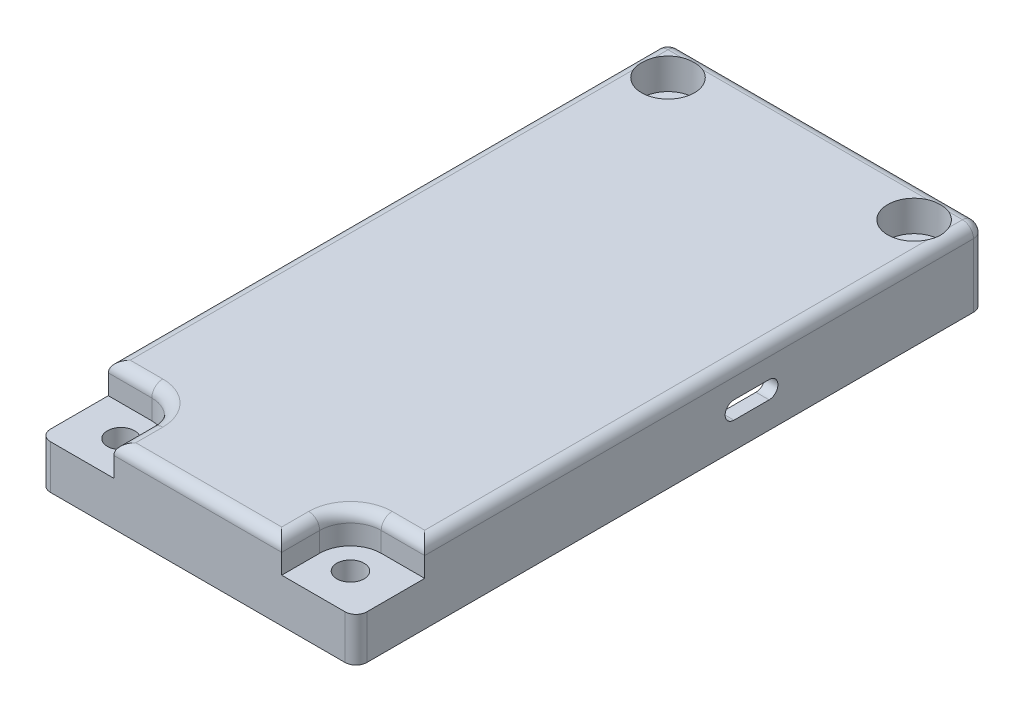
SolidWorks part; units mm, degrees
ref_plane "Front Plane" through (0, 0, 0) normal (0, 0, 1) x (1, 0, 0)
ref_plane "Top Plane" through (0, 0, 0) normal (0, 1, 0) x (1, 0, 0)
ref_plane "Right Plane" through (0, 0, 0) normal (1, 0, 0) x (0, 0, -1)
sketch "Sketch1" plane through (0, 0, 0) normal (0, 1, 0) x (1, 0, 0)
  line L1 (0, 0) -> (36, 0)
  line L2 (0, 0) -> (0, 71.5)
  line L3 (0, 71.5) -> (36, 71.5)
  line L4 (36, 0) -> (36, 71.5)
  dimension "D1" = 71.5
  dimension "D2" = 36
extrude "Boss-Extrude1" add sketch "Sketch1" along normal blind 8.5
sketch "Sketch2" plane through (0, 0, 0) normal (0, -1, 0) x (1, 0, 0)
  line L0 (0, -71.5) -> (0, 0) construction
  line L1 (1.5, -1.5) -> (34.5, -1.5)
  line L2 (1.5, -1.5) -> (1.5, -64.25)
  line L3 (1.5, -64.25) -> (34.5, -64.25)
  line L4 (34.5, -1.5) -> (34.5, -64.25)
  line L5 (0, 0) -> (36, 0) construction
  line L6 (36, 0) -> (36, -71.5) construction
  line L7 (36, -71.5) -> (0, -71.5) construction
  dimension "D1" = 1.5
  dimension "D2" = 1.5
  dimension "D3" = 1.5
  dimension "D4" = 7.25
extrude "Cut-Extrude1" cut sketch "Sketch2" against normal offset from surface (7 mm away) 1.5 up to face at (18, 8.5, -35.75)
sketch "Sketch4" plane through (0, 0, -71.5) normal (0, 0, -1) x (-1, 0, 0)
  line L0 (-36, 0) -> (0, 0) construction
  line L1 (-26, 0) -> (-10, 0)
  line L2 (-26, 0) -> (-26, 1.25)
  line L3 (-26, 1.25) -> (-10, 1.25)
  line L4 (-10, 0) -> (-10, 1.25)
  line L7 (-36, 8.5) -> (-36, 0) construction
  line L8 (0, 8.5) -> (0, 0) construction
  dimension "D1" = 10
  dimension "D2" = 10
  dimension "D3" = 1.25
extrude "Cut-Extrude2" cut sketch "Sketch4" against normal blind 6.5
fillet "Fillet1" radius 1.25 2 edges at (26, 1.25, -68.25) (10, 1.25, -68.25)
sketch "Sketch7" plane through (0, 7, 0) normal (0, -1, 0) x (1, 0, 0)
  line L0 (34.5, -1.5) -> (1.5, -1.5) construction
  line L1 (27.5, -1.5) -> (34.5, -1.5)
  line L2 (27.5, -1.5) -> (27.5, -8.5)
  line L3 (27.5, -8.5) -> (34.5, -8.5)
  line L4 (34.5, -1.5) -> (34.5, -8.5)
  line L5 (34.5, -1.5) -> (34.5, -64.25) construction
  line L6 (1.5, -1.5) -> (34.5, -1.5) construction
  line L7 (8.5, -1.5) -> (1.5, -1.5)
  line L8 (8.5, -1.5) -> (8.5, -8.5)
  line L9 (8.5, -8.5) -> (1.5, -8.5)
  line L10 (1.5, -1.5) -> (1.5, -8.5)
  line L11 (1.5, -64.25) -> (1.5, -1.5) construction
  dimension "D1" = 7
extrude "Boss-Extrude4" add sketch "Sketch7" along normal up to surface (7 mm away) up to face at (18, 0, -52)
sketch "Sketch8" plane through (0, 0, 0) normal (0, -1, 0) x (-1, 0, 0)
  line L0 (-36, 71.5) -> (-26, 71.5) construction
  line L1 (-36, 0) -> (-36, 71.5) construction
  line L2 (0, 71.5) -> (0, 0) construction
  line L3 (-8.5, 1.5) -> (-27.5, 1.5) construction
  circle A0 centre (-31.05, 4.32) radius 1.55
  circle A1 centre (-32, 67.5) radius 1.55
  circle A2 centre (-4, 67.5) radius 1.55
  circle A3 centre (-4.95, 4.32) radius 1.55
  point P8 (-3.2, 4.3343)
  point P11 (-18, 1.5)
  dimension "D7" = 3.1
  dimension "D1" = 4
  dimension "D2" = 4
  dimension "D3" = 4
  dimension "D4" = 13.05
  dimension "D5" = 13.05
  dimension "D6" = 4.32
extrude "Cut-Extrude3" cut sketch "Sketch8" against normal through all
sketch "Sketch9" plane through (0, 8.5, 0) normal (0, 1, 0) x (1, 0, 0)
  line L0 (4.95, 7.82) -> (0, 7.82)
  line L1 (0, 71.5) -> (0, 0) construction
  line L2 (0, 7.82) -> (0, 0)
  line L3 (0, 0) -> (8.45, 0)
  line L4 (0, 0) -> (36, 0) construction
  line L5 (8.45, 0) -> (8.45, 4.32)
  line L10 (27.55, 4.32) -> (27.55, 0)
  line L11 (27.55, 0) -> (36, 0)
  line L12 (36, 0) -> (36, 7.82)
  line L13 (36, 0) -> (36, 71.5) construction
  line L14 (36, 7.82) -> (31.05, 7.82)
  circle A0 centre (4, 67.5) radius 3
  circle A1 centre (32, 67.5) radius 3
  arc A3 (8.45, 4.32) -> (4.95, 7.82) centre (4.95, 4.32) ccw
  arc A4 (31.05, 7.82) -> (27.55, 4.32) centre (31.05, 4.32) ccw
  dimension "D1" = 6
  dimension "D2" = 3.5
  dimension "D3" = 3.5
extrude "Cut-Extrude4" cut sketch "Sketch9" against normal offset from surface (3.5 mm away) 5 up to face at (4.95, 0, -5.87)
sketch "Sketch10" plane through (34.5, 0, 0) normal (-1, 0, 0) x (0, 0, 1)
  line L0 (-47, 4) -> (-43, 4) construction
  line L1 (-47, 5) -> (-43, 5)
  line L2 (-47, 3) -> (-43, 3)
  line L3 (-8.5, 7) -> (-64.25, 7) construction
  line L5 (0, 5) -> (0, 0) construction
  arc A0 (-47, 5) -> (-47, 3) centre (-47, 4) ccw
  arc A1 (-43, 3) -> (-43, 5) centre (-43, 4) ccw
  point P2 (-45, 4)
  dimension "D1" = 2
  dimension "D2" = 4
  dimension "D3" = 3
  dimension "D4" = 45
extrude "Cut-Extrude5" cut sketch "Sketch10" against normal through all
sketch "Sketch11" plane through (0, 7, 0) normal (0, -1, 0) x (1, 0, 0)
  line L1 (34.5, -64.25) -> (1.5, -64.25) construction
  line L2 (1.5, -64.25) -> (6.5, -64.25)
  line L3 (1.5, -64.25) -> (1.5, -59.25)
  line L4 (1.5, -59.25) -> (6.5, -59.25)
  line L6 (6.5, -64.25) -> (6.5, -59.25)
  line L7 (1.5, -64.25) -> (1.5, -8.5) construction
  line L9 (34.5, -64.25) -> (29.5, -64.25)
  line L10 (34.5, -64.25) -> (34.5, -59.25)
  line L11 (34.5, -59.25) -> (29.5, -59.25)
  line L12 (29.5, -64.25) -> (29.5, -59.25)
  dimension "D1" = 5
extrude "Boss-Extrude8" add sketch "Sketch11" along normal offset from surface (4.31 mm away) 2.69 up to face at (4.95, 0, -5.87)
fillet "Fillet2" radius 1.25 14 edges at (18, 8.5, -71.5) (36, 8.5, -39.66) (33.525, 8.5, -7.82) (28.5751, 8.5, -6.7949) (27.55, 8.5, -2.16) (18, 8.5, 0) (8.45, 8.5, -2.16) (7.4249, 8.5, -6.7949) (2.475, 8.5, -7.82) (0, 8.5, -39.66) (0, 2.5, 0) (36, 2.5, 0) (36, 4.25, -71.5) (0, 4.25, -71.5)
